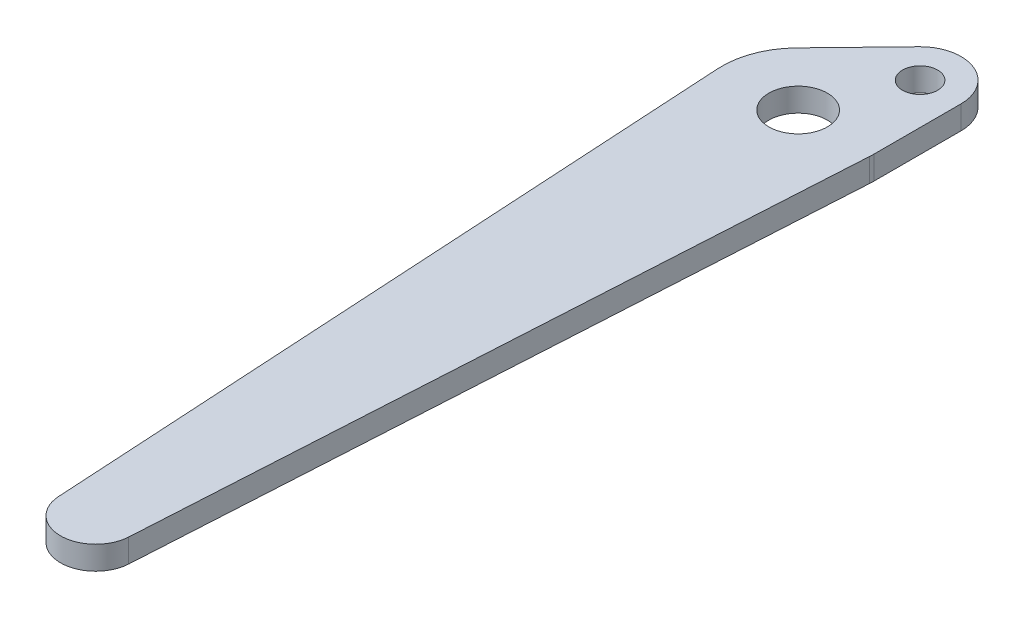
SolidWorks part; units mm, degrees
ref_plane "Front Plane" through (0, 0, 0) normal (0, 0, 1) x (1, 0, 0)
ref_plane "Top Plane" through (0, 0, 0) normal (0, 1, 0) x (1, 0, 0)
ref_plane "Right Plane" through (0, 0, 0) normal (1, 0, 0) x (0, 0, -1)
sketch "Sketch1" plane through (0, 0, 0) normal (0, 1, 0) x (1, 0, 0)
  line L0 (-5.9333, 5.7394) -> (0.6152, 12.509)
  line L1 (8.255, 9.4186) -> (8.255, 0)
  line L2 (8.2409, -0.4815) -> (3.8035, -76.4222)
  line L3 (-8.2409, -0.4815) -> (-3.8035, -76.4222)
  circle A0 centre (0, 0) radius 3.175
  circle A1 centre (3.81, 9.4186) radius 1.905
  arc A2 (-5.9333, 5.7394) -> (-8.2409, -0.4815) centre (0, 0) ccw
  arc A3 (8.255, 9.4186) -> (0.6152, 12.509) centre (3.81, 9.4186) ccw
  arc A4 (-3.8035, -76.4222) -> (3.8035, -76.4222) centre (0, -76.2) ccw
  arc A5 (8.2409, -0.4815) -> (8.255, 0) centre (0, 0) ccw
  point P6 (0.705, -28.0039)
  point P15 (0, 0)
  point P16 (0, -29.3576)
  point P17 (5.0811, 9.3373)
  dimension "D1" = 6.35
  dimension "D2" = 3.81
  dimension "D3" = 3.81
  dimension "D5" = 2.54
  dimension "D6" = 5.08
  dimension "D4" = 76.2
extrude "Boss-Extrude1" add sketch "Sketch1" along normal blind 2.54
